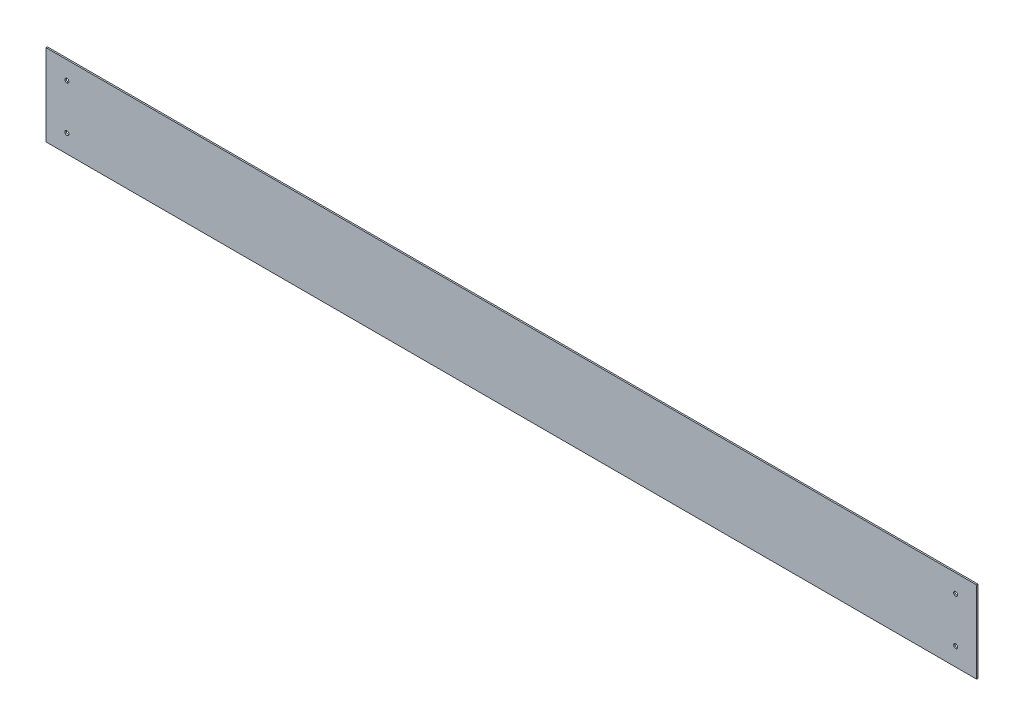
SolidWorks part; units mm, degrees
ref_plane "Front Plane" through (0, 0, 0) normal (0, 0, 1) x (1, 0, 0)
ref_plane "Top Plane" through (0, 0, 0) normal (0, 1, 0) x (1, 0, 0)
ref_plane "Right Plane" through (0, 0, 0) normal (1, 0, 0) x (0, 0, -1)
sketch "Sketch1" plane through (0, 0, 0) normal (0, 0, 1) x (1, 0, 0)
  line L1 (-513, -45) -> (513, -45)
  line L2 (-513, -45) -> (-513, 45)
  line L3 (-513, 45) -> (513, 45)
  line L4 (513, -45) -> (513, 45)
  line L5 (-513, -45) -> (513, 45) construction
  line L6 (-513, 45) -> (513, -45) construction
  point P0 (0, 0)
  dimension "D1" = 1026
  dimension "D2" = 90
extrude "Boss-Extrude1" add sketch "Sketch1" along normal blind 1.5875
hole_wizard "M4 Clearance Hole1" positions "Sketch2" profile "Sketch4" hole size "M4" standard "ANSI Metric" end condition through all
sketch "Sketch2" plane through (0, 0, 1.5875) normal (0, 0, 1) x (1, 0, 0)
  line L0 (-490, 25) -> (-490, -25)
  line L1 (513, 45) -> (-513, 45) construction
  line L2 (-513, -45) -> (513, -45) construction
  line L3 (-513, 45) -> (-513, -45) construction
  line L4 (0, -0.8731) -> (0, 0.8731) construction
  line L5 (490, 25) -> (490, -25)
  point P1 (-490, 25)
  point P2 (-490, -25)
  point P19 (490, -25)
  point P20 (490, 25)
  dimension "D1" = 20
  dimension "D2" = 20
  dimension "D3" = 23
sketch "Sketch4" plane through (-490, 25, 1.5875) normal (1, 0, 0) x (0, -1, 0)
  line L0 (0, 0) -> (0, 1.5875)
  line L1 (0, 1.5875) -> (2.25, 1.5875)
  line L2 (2.25, 1.5875) -> (2.25, 0)
  line L5 (2.25, 0) -> (0, 0)
  line L11 (0, -6.35) -> (0, 107.95) construction
  dimension "Thru Hole Dia." = 4.5
  dimension "Thru Hole Depth" = 1.5875
